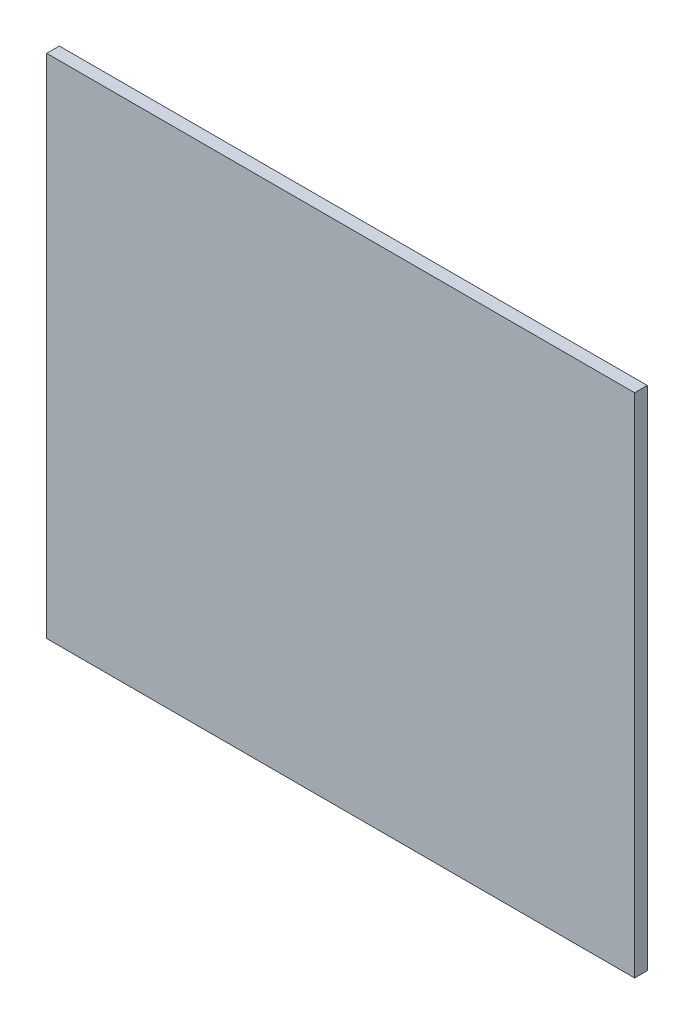
SolidWorks part; units mm, degrees
material "Pine"
ref_plane "Front Plane" through (0, 0, 0) normal (0, 0, 1) x (1, 0, 0)
ref_plane "Top Plane" through (0, 0, 0) normal (0, 1, 0) x (1, 0, 0)
ref_plane "Right Plane" through (0, 0, 0) normal (1, 0, 0) x (0, 0, -1)
sketch "Sketch2" plane through (0, 0, 0) normal (0, 0, 1) x (1, 0, 0)
  line L1 (-217.7984, 257.8858) -> (334.6516, 257.8858)
  line L2 (-217.7984, 257.8858) -> (-217.7984, -218.3642)
  line L3 (-217.7984, -218.3642) -> (334.6516, -218.3642)
  line L4 (334.6516, 257.8858) -> (334.6516, -218.3642)
  dimension "D1" = 552.45
  dimension "D2" = 476.25
extrude "Boss-Extrude1" add sketch "Sketch2" along normal blind 11.9062
